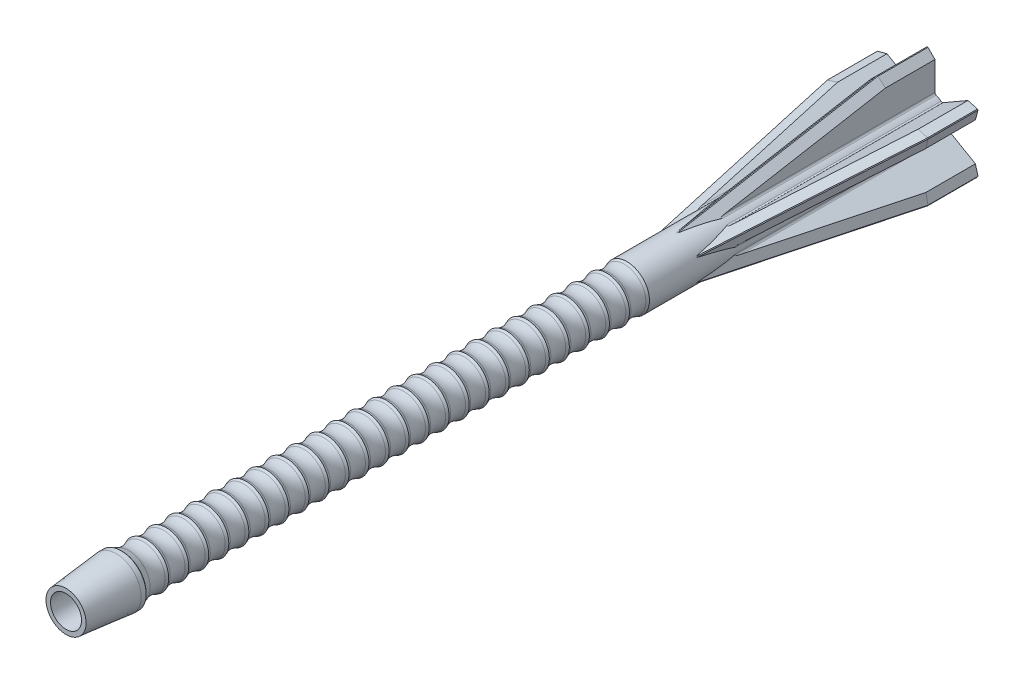
SolidWorks part; units mm, degrees
ref_plane "정면" through (0, 0, 0) normal (0, 0, 1) x (1, 0, 0)
ref_plane "윗면" through (0, 0, 0) normal (0, 1, 0) x (1, 0, 0)
ref_plane "우측면" through (0, 0, 0) normal (1, 0, 0) x (0, 0, -1)
sketch "스케치2" plane through (0, 0, 0) normal (0, 0, 1) x (1, 0, 0)
  circle A0 centre (0, 0) radius 2.25
  dimension "D1" = 4.5
extrude "보스-돌출1" add sketch "스케치2" along normal blind 30
sketch "스케치3" plane through (0, 0, 0) normal (1, 0, 0) x (0, 0, -1)
  line L0 (-30, 0) -> (-100, 0) construction
  line L1 (-30, 2.25) -> (-30, -2.25) construction
  line L2 (-30, 2.25) -> (-31, 1.85)
  line L3 (-31, 1.85) -> (-32, 2.25)
  line L4 (-32, 2.25) -> (-30, 2.25) construction
  line L5 (-32, 2.25) -> (-32, 0)
  line L6 (-32, 0) -> (-30, 0)
  line L7 (-30, 2.25) -> (-30, 0)
  dimension "D1" = 70
  dimension "D2" = 0.4
  dimension "D3" = 2
revolve "회전1" add sketch "스케치3" angle 360 about L0
fillet "필렛1" radius 2 1 edges at (0, 1.85, 31)
sketch "스케치4" plane through (0, 0, 0) normal (1, 0, 0) x (0, 0, -1)
  line L0 (0, 0) -> (-100, 0) construction
  dimension "D1" = 100
pattern_linear "선형 패턴1" count 25 spacing 2 along (0, 0, 1) of "회전1", "필렛1"
ref_plane "평면1" through (0, 0, 80) normal (0, 0, 1) x (1, 0, 0)
sketch "스케치6" plane through (0, 0, 80) normal (0, 0, 1) x (1, 0, 0)
  circle A0 centre (0, 0) radius 2.5
  dimension "D1" = 5
extrude "보스-돌출3" add sketch "스케치6" along normal blind 6
chamfer "모따기1" distance 5 distance2 0.5 1 edges at (2.5, 0, 86) first distance on face at (2.5, 0, 86)
chamfer "모따기2" distance 0.5 angle 45 1 edges at (2.5, 0, 80)
sketch "스케치8" plane through (0, 0, 0) normal (1, 0, 0) x (0, 0, -1)
  line L0 (0, 2.25) -> (0, 5.8)
  line L1 (0, 2.25) -> (-30, 2.25) construction
  line L2 (0, 5.8) -> (-5, 5.8)
  line L3 (-5, 5.8) -> (-25, 2.25)
  line L4 (-25, 2.25) -> (-25, 1.0213)
  line L5 (-25, 1.0213) -> (0, 1.0213)
  line L6 (0, 1.0213) -> (0, 2.25)
  line L7 (0, 0) -> (-25, 0) construction
  line L8 (0, 0) -> (-100, 0) construction
  line L9 (-25, 1.0213) -> (-25, 0) construction
  line L10 (0, 1.0213) -> (0, 0) construction
  line L11 (0, 0) -> (0, 5.8) construction
  line L12 (0, -2.25) -> (0, 2.25) construction
  dimension "D1" = 11.6
  dimension "D2" = 25
  dimension "D3" = 5
extrude "보스-돌출4" add sketch "스케치8" along normal mid plane 1.5
chamfer "모따기3" distance 0.7 angle 45 4 edges at (0.75, 5.8, 2.5) (0.75, 4.025, 15) (-0.75, 5.8, 2.5) (-0.75, 4.025, 15)
pattern_circular "원형 패턴1" count 6 over 360 about axis through (0, 0, 30) along (0, 0, -1) of "모따기3", "보스-돌출4"
sketch "스케치10" plane through (0, 0, 0) normal (0, 0, 1) x (1, 0, 0)
  circle A0 centre (0, 0) radius 1.5
  dimension "D1" = 3
extrude "컷-돌출3" cut sketch "스케치10" along normal blind 1
chamfer "모따기4" distance 1 angle 45 1 edges at (1.5, 0, 1)
fillet "필렛3" radius 0.2 12 edges at (1.4621, 1.7102, 10.8598) (2.2121, 0.4111, 10.8598) (0.75, 2.1213, 10.8598) (-0.75, 2.1213, 10.8598) (-1.4621, 1.7102, 10.8598) (-2.2121, 0.4111, 10.8598) (-2.2121, -0.4111, 10.8598) (-1.4621, -1.7102, 10.8598) (-0.75, -2.1213, 10.8598) (0.75, -2.1213, 10.8598) (1.4621, -1.7102, 10.8598) (2.2121, -0.4111, 10.8598)
sketch "스케치7" plane through (0, 0, 86) normal (0, 0, 1) x (1, 0, 0)
  circle A0 centre (0, 0) radius 1.55
  dimension "D1" = 3.1
extrude "컷-돌출1" cut sketch "스케치7" against normal blind 60
chamfer "모따기6" distance 0.4 angle 45 1 edges at (1.55, 0, 26)
